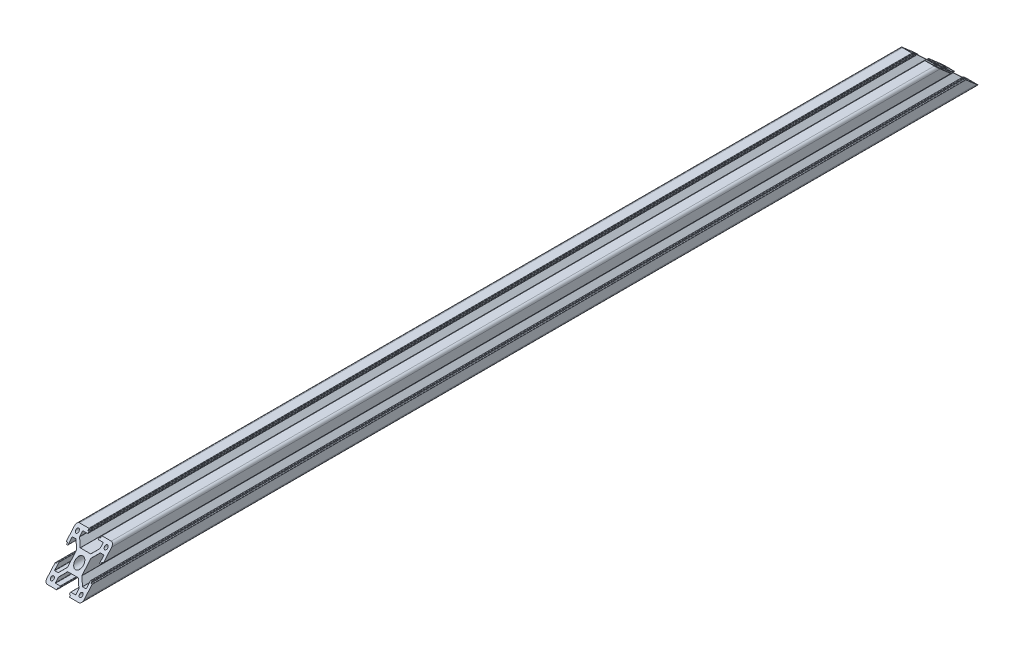
SolidWorks part; units mm, degrees
material "6063-T5"
ref_plane "Alzado" through (0, 0, 0) normal (0, 0, 1) x (1, 0, 0)
ref_plane "Planta" through (0, 0, 0) normal (0, 1, 0) x (1, 0, 0)
ref_plane "Vista lateral" through (0, 0, 0) normal (1, 0, 0) x (0, 0, -1)
sketch "Croquis1" plane through (0, 0, 0) normal (0, 0, 1) x (1, 0, 0)
  line L0 (0, 53.0989) -> (0, -48.4513) construction
  line L1 (-45.0818, 0) -> (46.476, 0) construction
  line L2 (-4.1615, 5.8) -> (4.1615, 5.8)
  line L3 (4.3029, 5.8586) -> (8.1914, 9.7471)
  line L4 (8.25, 9.8885) -> (8.25, 12.6)
  line L5 (8.05, 12.8) -> (4.3, 12.8)
  line L6 (4.1, 13) -> (4.1, 13.7)
  line L7 (4.3, 13.9) -> (4.9, 13.9)
  line L8 (5.1, 14.1) -> (5.1, 14.8)
  line L9 (5.3, 15) -> (12.8, 15)
  line L10 (0, 0) -> (45.9185, 45.9185) construction
  line L11 (15, 5.3) -> (15, 12.8)
  line L12 (13.9, 5.1) -> (14.8, 5.1)
  line L13 (13.9, 4.3) -> (13.9, 5.1)
  line L14 (13, 4.1) -> (13.7, 4.1)
  line L15 (12.8, 8.05) -> (12.8, 4.3)
  line L16 (9.8885, 8.25) -> (12.6, 8.25)
  line L17 (5.8586, 4.3029) -> (9.7471, 8.1914)
  line L18 (5.8, -4.1615) -> (5.8, 4.1615)
  line L19 (5.8586, -4.3029) -> (9.7471, -8.1914)
  line L20 (9.8885, -8.25) -> (12.6, -8.25)
  line L21 (12.8, -8.05) -> (12.8, -4.3)
  line L22 (13, -4.1) -> (13.7, -4.1)
  line L23 (13.9, -4.3) -> (13.9, -5.1)
  line L24 (13.9, -5.1) -> (14.8, -5.1)
  line L25 (15, -5.3) -> (15, -12.8)
  line L26 (5.3, -15) -> (12.8, -15)
  line L27 (5.1, -14.1) -> (5.1, -14.8)
  line L28 (4.3, -13.9) -> (4.9, -13.9)
  line L29 (4.1, -13) -> (4.1, -13.7)
  line L30 (8.05, -12.8) -> (4.3, -12.8)
  line L31 (8.25, -9.8885) -> (8.25, -12.6)
  line L32 (4.3029, -5.8586) -> (8.1914, -9.7471)
  line L33 (-4.1615, -5.8) -> (4.1615, -5.8)
  line L64 (-4.3029, -5.8586) -> (-8.1914, -9.7471)
  line L65 (-8.25, -9.8885) -> (-8.25, -12.6)
  line L66 (-8.05, -12.8) -> (-4.3, -12.8)
  line L67 (-4.1, -13) -> (-4.1, -13.7)
  line L68 (-4.3, -13.9) -> (-4.9, -13.9)
  line L69 (-5.1, -14.1) -> (-5.1, -14.8)
  line L70 (-5.3, -15) -> (-12.8, -15)
  line L71 (-15, -5.3) -> (-15, -12.8)
  line L72 (-13.9, -5.1) -> (-14.8, -5.1)
  line L73 (-13.9, -4.3) -> (-13.9, -5.1)
  line L74 (-13, -4.1) -> (-13.7, -4.1)
  line L75 (-12.8, -8.05) -> (-12.8, -4.3)
  line L76 (-9.8885, -8.25) -> (-12.6, -8.25)
  line L77 (-5.8586, -4.3029) -> (-9.7471, -8.1914)
  line L78 (-5.8586, 4.3029) -> (-9.7471, 8.1914)
  line L79 (-9.8885, 8.25) -> (-12.6, 8.25)
  line L80 (-12.8, 8.05) -> (-12.8, 4.3)
  line L81 (-13, 4.1) -> (-13.7, 4.1)
  line L82 (-13.9, 4.3) -> (-13.9, 5.1)
  line L83 (-13.9, 5.1) -> (-14.8, 5.1)
  line L84 (-15, 5.3) -> (-15, 12.8)
  line L85 (-5.3, 15) -> (-12.8, 15)
  line L86 (-5.1, 14.1) -> (-5.1, 14.8)
  line L87 (-4.3, 13.9) -> (-4.9, 13.9)
  line L88 (-4.1, 13) -> (-4.1, 13.7)
  line L89 (-8.05, 12.8) -> (-4.3, 12.8)
  line L90 (-8.25, 9.8885) -> (-8.25, 12.6)
  line L91 (-4.3029, 5.8586) -> (-8.1914, 9.7471)
  line L106 (-5.8, -4.1615) -> (-5.8, 4.1615)
  arc A0 (12.8, 15) -> (15, 12.8) centre (12.8, 12.8) cw
  arc A1 (5.1, 14.8) -> (5.3, 15) centre (5.3, 14.8) cw
  arc A2 (4.9, 13.9) -> (5.1, 14.1) centre (4.9, 14.1) ccw
  arc A3 (4.1, 13.7) -> (4.3, 13.9) centre (4.3, 13.7) cw
  arc A4 (4.3, 12.8) -> (4.1, 13) centre (4.3, 13) cw
  arc A5 (8.25, 12.6) -> (8.05, 12.8) centre (8.05, 12.6) ccw
  arc A6 (4.1615, 5.8) -> (4.3029, 5.8586) centre (4.1615, 6) ccw
  arc A7 (8.1914, 9.7471) -> (8.25, 9.8885) centre (8.05, 9.8885) ccw
  arc A8 (13, 4.1) -> (12.8, 4.3) centre (13, 4.3) cw
  arc A9 (5.8586, 4.3029) -> (5.8, 4.1615) centre (6, 4.1615) ccw
  arc A10 (9.8885, 8.25) -> (9.7471, 8.1914) centre (9.8885, 8.05) ccw
  arc A11 (12.8, 8.05) -> (12.6, 8.25) centre (12.6, 8.05) ccw
  arc A12 (13.9, 4.3) -> (13.7, 4.1) centre (13.7, 4.3) cw
  arc A13 (15, 5.3) -> (14.8, 5.1) centre (14.8, 5.3) cw
  arc A16 (15, -5.3) -> (14.8, -5.1) centre (14.8, -5.3) ccw
  arc A17 (13.9, -4.3) -> (13.7, -4.1) centre (13.7, -4.3) ccw
  arc A18 (12.8, -8.05) -> (12.6, -8.25) centre (12.6, -8.05) cw
  arc A19 (9.8885, -8.25) -> (9.7471, -8.1914) centre (9.8885, -8.05) cw
  arc A20 (5.8586, -4.3029) -> (5.8, -4.1615) centre (6, -4.1615) cw
  arc A21 (13, -4.1) -> (12.8, -4.3) centre (13, -4.3) ccw
  arc A22 (8.1914, -9.7471) -> (8.25, -9.8885) centre (8.05, -9.8885) cw
  arc A23 (4.1615, -5.8) -> (4.3029, -5.8586) centre (4.1615, -6) cw
  arc A24 (8.25, -12.6) -> (8.05, -12.8) centre (8.05, -12.6) cw
  arc A25 (4.3, -12.8) -> (4.1, -13) centre (4.3, -13) ccw
  arc A26 (4.1, -13.7) -> (4.3, -13.9) centre (4.3, -13.7) ccw
  arc A27 (4.9, -13.9) -> (5.1, -14.1) centre (4.9, -14.1) cw
  arc A28 (5.1, -14.8) -> (5.3, -15) centre (5.3, -14.8) ccw
  arc A29 (12.8, -15) -> (15, -12.8) centre (12.8, -12.8) ccw
  circle A44 centre (11.625, 11.625) radius 1.25
  circle A45 centre (11.625, -11.625) radius 1.25
  arc A60 (-12.8, -15) -> (-15, -12.8) centre (-12.8, -12.8) cw
  arc A61 (-5.1, -14.8) -> (-5.3, -15) centre (-5.3, -14.8) cw
  arc A62 (-4.9, -13.9) -> (-5.1, -14.1) centre (-4.9, -14.1) ccw
  arc A63 (-4.1, -13.7) -> (-4.3, -13.9) centre (-4.3, -13.7) cw
  arc A64 (-4.3, -12.8) -> (-4.1, -13) centre (-4.3, -13) cw
  arc A65 (-8.25, -12.6) -> (-8.05, -12.8) centre (-8.05, -12.6) ccw
  arc A66 (-4.1615, -5.8) -> (-4.3029, -5.8586) centre (-4.1615, -6) ccw
  arc A67 (-8.1914, -9.7471) -> (-8.25, -9.8885) centre (-8.05, -9.8885) ccw
  arc A68 (-13, -4.1) -> (-12.8, -4.3) centre (-13, -4.3) cw
  arc A69 (-5.8586, -4.3029) -> (-5.8, -4.1615) centre (-6, -4.1615) ccw
  arc A70 (-9.8885, -8.25) -> (-9.7471, -8.1914) centre (-9.8885, -8.05) ccw
  arc A71 (-12.8, -8.05) -> (-12.6, -8.25) centre (-12.6, -8.05) ccw
  arc A72 (-13.9, -4.3) -> (-13.7, -4.1) centre (-13.7, -4.3) cw
  arc A73 (-15, -5.3) -> (-14.8, -5.1) centre (-14.8, -5.3) cw
  arc A76 (-15, 5.3) -> (-14.8, 5.1) centre (-14.8, 5.3) ccw
  arc A77 (-13.9, 4.3) -> (-13.7, 4.1) centre (-13.7, 4.3) ccw
  arc A78 (-12.8, 8.05) -> (-12.6, 8.25) centre (-12.6, 8.05) cw
  arc A79 (-9.8885, 8.25) -> (-9.7471, 8.1914) centre (-9.8885, 8.05) cw
  arc A80 (-5.8586, 4.3029) -> (-5.8, 4.1615) centre (-6, 4.1615) cw
  arc A81 (-13, 4.1) -> (-12.8, 4.3) centre (-13, 4.3) ccw
  arc A82 (-8.1914, 9.7471) -> (-8.25, 9.8885) centre (-8.05, 9.8885) cw
  arc A83 (-4.1615, 5.8) -> (-4.3029, 5.8586) centre (-4.1615, 6) cw
  arc A84 (-8.25, 12.6) -> (-8.05, 12.8) centre (-8.05, 12.6) cw
  arc A85 (-4.3, 12.8) -> (-4.1, 13) centre (-4.3, 13) ccw
  arc A86 (-4.1, 13.7) -> (-4.3, 13.9) centre (-4.3, 13.7) ccw
  arc A87 (-4.9, 13.9) -> (-5.1, 14.1) centre (-4.9, 14.1) cw
  arc A88 (-5.1, 14.8) -> (-5.3, 15) centre (-5.3, 14.8) ccw
  arc A89 (-12.8, 15) -> (-15, 12.8) centre (-12.8, 12.8) ccw
  circle A104 centre (-11.625, -11.625) radius 1.25
  circle A105 centre (-11.625, 11.625) radius 1.25
  circle A120 centre (0, 0) radius 3.4
  point P5 (-15, -15)
  point P26 (15, 15)
  point P29 (5.1, 15)
  point P32 (5.1, 13.9)
  point P35 (4.1, 13.9)
  point P38 (4.1, 12.8)
  point P41 (8.25, 12.8)
  point P44 (4.2444, 5.8)
  point P47 (8.25, 9.8056)
  point P50 (12.8, 4.1)
  point P53 (5.8, 4.2444)
  point P56 (9.8056, 8.25)
  point P59 (12.8, 8.25)
  point P62 (13.9, 4.1)
  point P65 (15, 5.1)
  point P112 (5.8, 0)
  point P113 (0, 5.8)
  point P114 (15, -5.1)
  point P115 (13.9, -4.1)
  point P116 (12.8, -8.25)
  point P117 (9.8056, -8.25)
  point P118 (5.8, -4.2444)
  point P119 (12.8, -4.1)
  point P120 (8.25, -9.8056)
  point P121 (4.2444, -5.8)
  point P122 (8.25, -12.8)
  point P123 (4.1, -12.8)
  point P124 (4.1, -13.9)
  point P125 (5.1, -13.9)
  point P126 (5.1, -15)
  point P127 (15, -15)
  point P222 (0, -5.8)
  point P223 (-5.1, -15)
  point P224 (-5.1, -13.9)
  point P225 (-4.1, -13.9)
  point P226 (-4.1, -12.8)
  point P227 (-8.25, -12.8)
  point P228 (-4.2444, -5.8)
  point P229 (-8.25, -9.8056)
  point P230 (-12.8, -4.1)
  point P231 (-5.8, -4.2444)
  point P232 (-9.8056, -8.25)
  point P233 (-12.8, -8.25)
  point P234 (-13.9, -4.1)
  point P235 (-15, -5.1)
  point P236 (-5.8, 0)
  point P237 (-15, 5.1)
  point P238 (-13.9, 4.1)
  point P239 (-12.8, 8.25)
  point P240 (-9.8056, 8.25)
  point P241 (-5.8, 4.2444)
  point P242 (-12.8, 4.1)
  point P243 (-8.25, 9.8056)
  point P244 (-4.2444, 5.8)
  point P245 (-8.25, 12.8)
  point P246 (-4.1, 12.8)
  point P247 (-4.1, 13.9)
  point P248 (-5.1, 13.9)
  point P249 (-5.1, 15)
  point P250 (-15, 15)
  dimension "D8" = 2.2
  dimension "D9" = 0.2
  dimension "D12" = 6.8
  dimension "D1" = 2.2
  dimension "D2" = 8.25
  dimension "D3" = 15
  dimension "D4" = 9.2
  dimension "D5" = 4.1
  dimension "D6" = 5.1
  dimension "D7" = 2.2
  dimension "D11" = 3.375
extrude "Saliente-Extruir1" add sketch "Croquis1" along normal blind 725
sketch "Sketch1" plane through (0, 0, 0) normal (1, 0, 0) x (0, 0, -1)
  line L0 (-725, -15) -> (-698.9214, 15)
  line L1 (-725, 15) -> (0, 15) construction
  line L2 (-725, -15) -> (0, -15) construction
  line L3 (-698.9214, 15) -> (-725, 15)
  line L4 (-725, 15) -> (-725, -15)
  line L5 (-362.5, 141.1023) -> (-362.5, -105.3974) construction
  line L6 (-725, -4.1615) -> (-725, 4.1615) construction
  line L7 (0, -4.1615) -> (0, 4.1615) construction
  line L8 (0, 15) -> (0, -15)
  line L9 (-34.5111, 15) -> (0, 15)
  line L10 (0, -15) -> (-34.5111, 15)
  dimension "D1" = 49
extrude "Cut-Extrude1" cut sketch "Sketch1" against normal through all both and the other way through all
